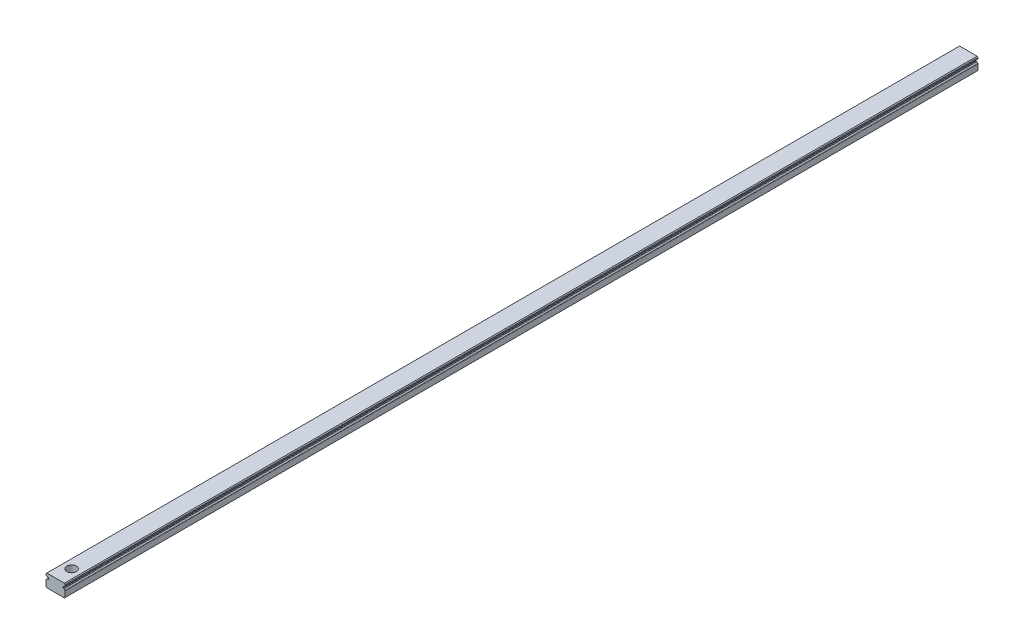
SolidWorks part; units mm, degrees
ref_plane "Front Plane" through (0, 0, 0) normal (0, 0, 1) x (1, 0, 0)
ref_plane "Top Plane" through (0, 0, 0) normal (0, 1, 0) x (1, 0, 0)
ref_plane "Right Plane" through (0, 0, 0) normal (1, 0, 0) x (0, 0, -1)
sketch "Sketch1" plane through (0, 0, 0) normal (0, 0, 1) x (1, 0, 0)
  line L0 (-6, 0) -> (6, 0) construction
  line L1 (0, -4) -> (0, 4) construction
  line L2 (0, 4) -> (0, -4) construction
  line L3 (-3, 4) -> (3, 4) construction
  line L4 (-1.75, -0.5) -> (1.75, -0.5) construction
  point P0 (0, -0.5)
  point P3 (-6, -4)
  point P4 (0, 0)
  point P8 (0, 0)
  point P11 (0, 4)
  point P15 (0, 4)
  point P17 (0, -0.5)
  point P18 (6, 4)
  point P20 (-6, 4)
  dimension "Rail Width" = 12
  dimension "Rail Height" = 8
  dimension "Mounting Hole Depth" = 3.5
  dimension "Mounting Hole Counterbore Diameter" = 6
  dimension "Mounting Hole Diameter" = 3.5
sketch "Sketch2" plane through (0, 0, 0) normal (1, 0, 0) x (0, 0, -1)
  line L0 (285, 0) -> (-285, 0) construction
  line L1 (-11.5, 4) -> (11.5, 4) construction
  line L3 (0, 4) -> (0, 0) construction
  point P0 (-275, 0)
  point P4 (0, 0)
  point P5 (-250, 0)
  point P6 (-262.5, 0)
  point P9 (-275, 4)
  point P10 (0, 4)
  point P11 (285, 4)
  point P13 (-285, 4)
  point P14 (262.5, 0)
  point P17 (-285, -4)
  dimension "Rail Length" = 570
  dimension "Mounting Hole Center to Edge" = 10
  dimension "Mounting Hole Center to Center" = 25
  dimension "Number of Mounting Holes" = 23
  dimension "Break Line" = 12.5
sketch "Sketch3" plane through (0, 0, 0) normal (0, 0, 1) x (1, 0, 0)
  point P0 (0, 4)
  line B0 (-6, 0.1421) -> (-6, -3.5)
  line B1 (-6, -3.5) -> (-5.5, -4)
  line B2 (-5.5, -4) -> (1.6, -4)
  line B3 (2.4, -4) -> (5.5, -4)
  line B4 (5.5, -4) -> (6, -3.5)
  line B5 (6, -3.5) -> (6, 0.1421)
  line B6 (5.0738, 0.9945) -> (4.7282, 1.0247)
  line B7 (4.5, 1.2738) -> (4.5, 1.7262)
  line B8 (4.7282, 1.9753) -> (5.0948, 2.0073)
  line B9 (6, 2.8254) -> (6, 3.5)
  line B10 (6, 3.5) -> (5.5, 4)
  line B11 (5.5, 4) -> (-5.5, 4)
  line B12 (-5.5, 4) -> (-6, 3.5)
  line B13 (-6, 3.5) -> (-6, 2.8254)
  line B14 (-5.0948, 2.0073) -> (-4.7282, 1.9753)
  line B15 (-4.5, 1.7262) -> (-4.5, 1.2738)
  line B16 (-4.7282, 1.0247) -> (-5.0738, 0.9945)
  arc B17 (-5.8448, 0.3734) -> (-6, 0.1421) centre (-5.75, 0.1421) ccw
  arc B18 (2.4, -4) -> (1.6, -4) centre (2, -4.3) ccw
  arc B19 (6, 0.1421) -> (5.8448, 0.3734) centre (5.75, 0.1421) ccw
  arc B20 (5.2672, 0.8728) -> (5.8448, 0.3734) centre (6.3, 1.4838) ccw
  arc B21 (5.2672, 0.8728) -> (5.0738, 0.9945) centre (5.052, 0.7455) ccw
  arc B22 (4.5, 1.2738) -> (4.7282, 1.0247) centre (4.75, 1.2738) ccw
  arc B23 (4.7282, 1.9753) -> (4.5, 1.7262) centre (4.75, 1.7262) ccw
  arc B24 (5.0948, 2.0073) -> (5.2845, 2.1232) centre (5.073, 2.2564) ccw
  arc B25 (5.8448, 2.5941) -> (5.2845, 2.1232) centre (6.3, 1.4838) ccw
  arc B26 (5.8448, 2.5941) -> (6, 2.8254) centre (5.75, 2.8254) ccw
  arc B27 (-6, 2.8254) -> (-5.8448, 2.5941) centre (-5.75, 2.8254) ccw
  arc B28 (-5.2845, 2.1232) -> (-5.8448, 2.5941) centre (-6.3, 1.4838) ccw
  arc B29 (-5.2845, 2.1232) -> (-5.0948, 2.0073) centre (-5.073, 2.2564) ccw
  arc B30 (-4.5, 1.7262) -> (-4.7282, 1.9753) centre (-4.75, 1.7262) ccw
  arc B31 (-4.7282, 1.0247) -> (-4.5, 1.2738) centre (-4.75, 1.2738) ccw
  arc B32 (-5.0738, 0.9945) -> (-5.2672, 0.8728) centre (-5.052, 0.7455) ccw
  arc B33 (-5.8448, 0.3734) -> (-5.2672, 0.8728) centre (-6.3, 1.4838) ccw
sketch_block_instance "12mm Block-1"
sketch_block "12mm Block"
extrude "Boss-Extrude1" add sketch "Sketch3" against normal up to vertex (285 mm away) from vertex up to point (0, 0, -285) starting at point (0, 0, 285)
ref_plane "Plane1" through (0, 0, 275) normal (0, 0, 1) x (1, 0, 0)
sketch "Sketch4" plane through (0, 0, 275) normal (0, 0, 1) x (1, 0, 0)
  line L0 (0, 4) -> (0, -4)
  line L1 (0, -4) -> (-1.75, -4)
  line L3 (-1.75, -4) -> (-1.75, -0.5)
  line L4 (-1.75, -0.5) -> (-3, -0.5)
  line L5 (-3, -0.5) -> (-3, 4)
  line L6 (-3, 4) -> (0, 4)
revolve "Cut-Revolve1" cut sketch "Sketch4" angle 360 about L0
sketch "Sketch6" plane through (0, 0, 0) normal (1, 0, 0) x (0, 0, -1)
  line L0 (-272, -0.5) -> (-278, -0.5) construction
  line L5 (-272, -0.5) -> (-278, -0.5)
  line L17 (-276.75, -0.5) -> (-276.75, -4) construction
  line L18 (-273.25, -4) -> (-273.25, -0.5) construction
  line L32 (-272, -0.5) -> (-272, 4) construction
  line L33 (-278, 4) -> (-278, -0.5) construction
  line L34 (-276.75, -0.5) -> (-276.75, -4)
  line L35 (-273.25, -4) -> (-273.25, -0.5)
  line L36 (-272, -0.5) -> (-272, 4)
  line L37 (-278, 4) -> (-278, -0.5)
  line L38 (0, 4) -> (0, -4) construction
  line L40 (278, 4) -> (278, -0.5)
  line L41 (272, -0.5) -> (272, 4)
  line L42 (273.25, -4) -> (273.25, -0.5)
  line L43 (276.75, -0.5) -> (276.75, -4)
  line L44 (272, -0.5) -> (278, -0.5)
sketch "Sketch7" plane through (0, 0, 0) normal (0, 0, 1) x (1, 0, 0)
  line L0 (3, -0.5) -> (3, 4) construction
  line L1 (-3, 4) -> (-3, -0.5) construction
  line L2 (3, -0.5) -> (3, 4)
  line L3 (-3, 4) -> (-3, -0.5)
  line L4 (1.75, -3.867) -> (1.75, -0.5) construction
  line L11 (1.75, -3.867) -> (1.75, -0.5)
  line L18 (-1.75, -0.5) -> (-1.75, -4) construction
  line L32 (3, -0.5) -> (-3, -0.5) construction
  line L34 (-1.75, -0.5) -> (-1.75, -4)
  line L37 (3, -0.5) -> (-3, -0.5)
pattern_linear "LPattern1" count 1 spacing 25 along (0, 0, -1) rebuild error yes
equation "\"D3@LPattern1\"=\"Mounting Hole Center to Center@Sketch2\""
equation "\"D1@LPattern1\"=\"Number of Mounting Holes@Sketch2\""
equation "\"Break Line@Sketch2\"=\"Mounting Hole Center to Center@Sketch2\"/2"
